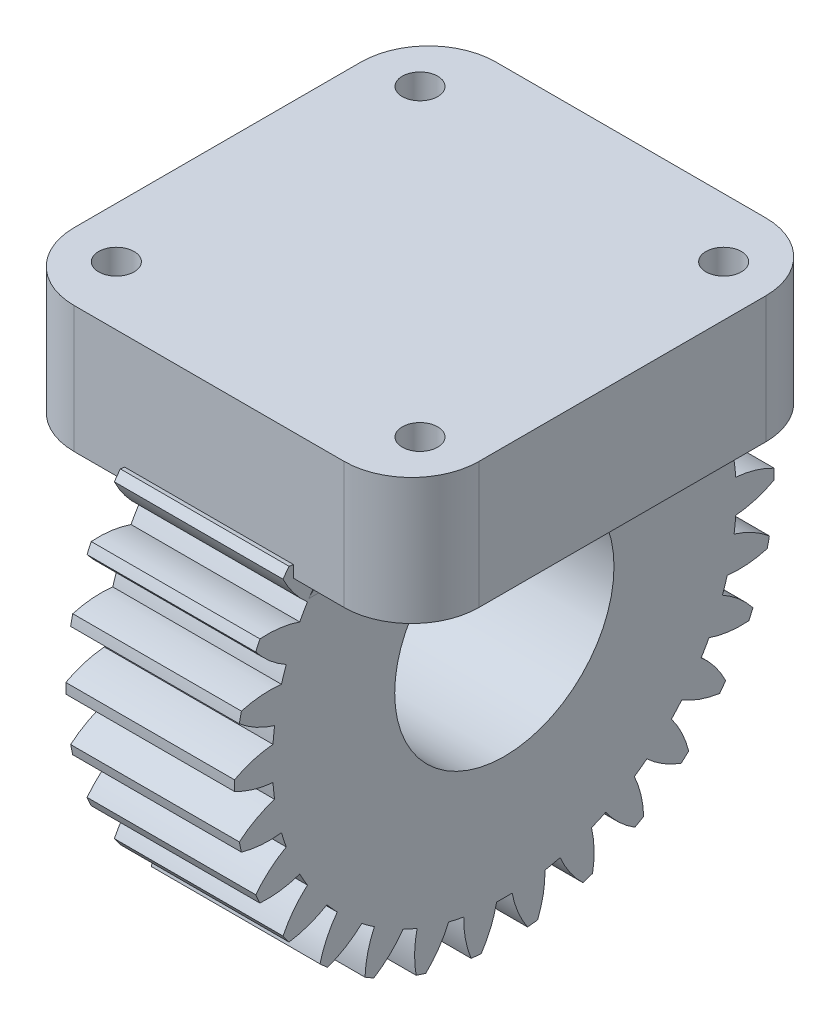
SolidWorks part; units mm, degrees
ref_plane "Front Plane" through (0, 0, 0) normal (0, 0, 1) x (1, 0, 0)
ref_plane "Top Plane" through (0, 0, 0) normal (0, 1, 0) x (1, 0, 0)
ref_plane "Right Plane" through (0, 0, 0) normal (1, 0, 0) x (0, 0, -1)
ref_plane "Plane1" through (30.4852, 0, 0) normal (1, 0, 0) x (0, 0, -1)
sketch "Sketch1" plane through (30.4852, 0, 0) normal (1, 0, 0) x (0, 0, -1)
  circle A0 centre (-23.9245, -5.8647) radius 13
  arc A1 (-55.9188, -6.4669) -> (-51.3536, -7.824) centre (-50.2847, 4.1283) ccw
  arc A2 (-51.3536, -7.824) -> (-51.1616, -9.6511) centre (-23.9245, -5.8647) ccw
  arc A3 (-51.1616, -9.6511) -> (-55.3448, -11.9278) centre (-47.631, -21.1199) ccw
  arc A4 (-55.3448, -11.9278) -> (-55.0945, -13.1057) centre (-23.9245, -5.8647) ccw
  arc A5 (-55.0945, -13.1057) -> (-50.3468, -13.4841) centre (-51.7863, -1.5707) ccw
  arc A6 (-50.3468, -13.4841) -> (-49.7791, -15.2312) centre (-23.9245, -5.8647) ccw
  arc A7 (-49.7791, -15.2312) -> (-53.3977, -18.3279) centre (-43.9412, -25.7154) ccw
  arc A8 (-53.3977, -18.3279) -> (-52.9079, -19.4281) centre (-23.9245, -5.8647) ccw
  arc A9 (-52.9079, -19.4281) -> (-48.1853, -18.8111) centre (-52.0702, -7.4573) ccw
  arc A10 (-48.1853, -18.8111) -> (-47.2667, -20.402) centre (-23.9245, -5.8647) ccw
  arc A11 (-47.2667, -20.402) -> (-50.1624, -24.1834) centre (-39.3766, -29.4434) ccw
  arc A12 (-50.1624, -24.1834) -> (-49.4545, -25.1577) centre (-23.9245, -5.8647) ccw
  arc A13 (-49.4545, -25.1577) -> (-44.9634, -23.5723) centre (-51.1241, -13.2744) ccw
  arc A14 (-44.9634, -23.5723) -> (-43.7342, -24.9375) centre (-23.9245, -5.8647) ccw
  arc A15 (-43.7342, -24.9375) -> (-45.7803, -29.2383) centre (-34.1367, -32.1408) ccw
  arc A16 (-45.7803, -29.2383) -> (-44.8854, -30.0441) centre (-23.9245, -5.8647) ccw
  arc A17 (-44.8854, -30.0441) -> (-40.8221, -27.5596) centre (-48.9891, -18.7676) ccw
  arc A18 (-40.8221, -27.5596) -> (-39.3358, -28.6394) centre (-23.9245, -5.8647) ccw
  arc A19 (-39.3358, -28.6394) -> (-40.4431, -33.2716) centre (-28.4504, -33.6898) ccw
  arc A20 (-40.4431, -33.2716) -> (-39.4002, -33.8737) centre (-23.9245, -5.8647) ccw
  arc A21 (-39.4002, -33.8737) -> (-35.9422, -30.5987) centre (-45.7588, -23.6968) ccw
  arc A22 (-35.9422, -30.5987) -> (-34.264, -31.3459) centre (-23.9245, -5.8647) ccw
  arc A23 (-34.264, -31.3459) -> (-34.3839, -36.1071) centre (-22.5663, -34.0228) ccw
  arc A24 (-34.3839, -36.1071) -> (-33.2386, -36.4792) centre (-23.9245, -5.8647) ccw
  arc A25 (-33.2386, -36.4792) -> (-30.5371, -32.5568) centre (-41.5741, -27.8468) ccw
  arc A26 (-30.5371, -32.5568) -> (-28.7402, -32.9388) centre (-23.9245, -5.8647) ccw
  arc A27 (-28.7402, -32.9388) -> (-27.8676, -37.6209) centre (-16.7416, -33.1251) ccw
  arc A28 (-27.8676, -37.6209) -> (-26.67, -37.7467) centre (-23.9245, -5.8647) ccw
  arc A29 (-26.67, -37.7467) -> (-24.843, -33.3484) centre (-36.6181, -31.036) ccw
  arc A30 (-24.843, -33.3484) -> (-23.0059, -33.3484) centre (-23.9245, -5.8647) ccw
  arc A31 (-23.0059, -33.3484) -> (-21.179, -37.7467) centre (-11.2308, -31.036) ccw
  arc A32 (-21.179, -37.7467) -> (-19.9813, -37.6209) centre (-23.9245, -5.8647) ccw
  arc A33 (-19.9813, -37.6209) -> (-19.1088, -32.9388) centre (-31.1073, -33.1251) ccw
  arc A34 (-19.1088, -32.9388) -> (-17.3118, -32.5568) centre (-23.9245, -5.8647) ccw
  arc A35 (-17.3118, -32.5568) -> (-14.6103, -36.4792) centre (-6.2748, -27.8468) ccw
  arc A36 (-14.6103, -36.4792) -> (-13.465, -36.1071) centre (-23.9245, -5.8647) ccw
  arc A37 (-13.465, -36.1071) -> (-13.585, -31.3459) centre (-25.2826, -34.0228) ccw
  arc A38 (-13.585, -31.3459) -> (-11.9067, -30.5987) centre (-23.9245, -5.8647) ccw
  arc A39 (-11.9067, -30.5987) -> (-8.4488, -33.8737) centre (-2.0902, -23.6968) ccw
  arc A40 (-8.4488, -33.8737) -> (-7.4059, -33.2716) centre (-23.9245, -5.8647) ccw
  arc A41 (-7.4059, -33.2716) -> (-8.5131, -28.6394) centre (-19.3986, -33.6898) ccw
  arc A42 (-8.5131, -28.6394) -> (-7.0269, -27.5596) centre (-23.9245, -5.8647) ccw
  arc A43 (-7.0269, -27.5596) -> (-2.9636, -30.0441) centre (1.1402, -18.7676) ccw
  arc A44 (-2.9636, -30.0441) -> (-2.0686, -29.2383) centre (-23.9245, -5.8647) ccw
  arc A45 (-2.0686, -29.2383) -> (-4.1148, -24.9375) centre (-13.7123, -32.1408) ccw
  arc A46 (-4.1148, -24.9375) -> (-2.8855, -23.5723) centre (-23.9245, -5.8647) ccw
  arc A47 (-2.8855, -23.5723) -> (1.6056, -25.1577) centre (3.2751, -13.2744) ccw
  arc A48 (1.6056, -25.1577) -> (2.3134, -24.1834) centre (-23.9245, -5.8647) ccw
  arc A49 (2.3134, -24.1834) -> (-0.5822, -20.402) centre (-8.4724, -29.4434) ccw
  arc A50 (-0.5822, -20.402) -> (0.3363, -18.8111) centre (-23.9245, -5.8647) ccw
  arc A51 (0.3363, -18.8111) -> (5.0589, -19.4281) centre (4.2213, -7.4573) ccw
  arc A52 (5.0589, -19.4281) -> (5.5487, -18.3279) centre (-23.9245, -5.8647) ccw
  arc A53 (5.5487, -18.3279) -> (1.9302, -15.2312) centre (-3.9078, -25.7154) ccw
  arc A54 (1.9302, -15.2312) -> (2.4979, -13.4841) centre (-23.9245, -5.8647) ccw
  arc A55 (2.4979, -13.4841) -> (7.2455, -13.1057) centre (3.9373, -1.5707) ccw
  arc A56 (7.2455, -13.1057) -> (7.4959, -11.9278) centre (-23.9245, -5.8647) ccw
  arc A57 (7.4959, -11.9278) -> (3.3126, -9.6511) centre (-0.218, -21.1199) ccw
  arc A58 (3.3126, -9.6511) -> (3.5046, -7.824) centre (-23.9245, -5.8647) ccw
  arc A59 (3.5046, -7.824) -> (8.0699, -6.4669) centre (2.4357, 4.1283) ccw
  arc A60 (8.0699, -6.4669) -> (8.0699, -5.2626) centre (-23.9245, -5.8647) ccw
  arc A61 (8.0699, -5.2626) -> (3.5046, -3.9054) centre (2.4357, -15.8577) ccw
  arc A62 (3.5046, -3.9054) -> (3.3126, -2.0784) centre (-23.9245, -5.8647) ccw
  arc A63 (3.3126, -2.0784) -> (7.4959, 0.1983) centre (-0.218, 9.3905) ccw
  arc A64 (7.4959, 0.1983) -> (7.2455, 1.3762) centre (-23.9245, -5.8647) ccw
  arc A65 (7.2455, 1.3762) -> (2.4979, 1.7546) centre (3.9373, -10.1588) ccw
  arc A66 (2.4979, 1.7546) -> (1.9302, 3.5018) centre (-23.9245, -5.8647) ccw
  arc A67 (1.9302, 3.5018) -> (5.5487, 6.5985) centre (-3.9078, 13.986) ccw
  arc A68 (5.5487, 6.5985) -> (5.0589, 7.6986) centre (-23.9245, -5.8647) ccw
  arc A69 (5.0589, 7.6986) -> (0.3363, 7.0816) centre (4.2213, -4.2721) ccw
  arc A70 (0.3363, 7.0816) -> (-0.5822, 8.6726) centre (-23.9245, -5.8647) ccw
  arc A71 (-0.5822, 8.6726) -> (2.3134, 12.4539) centre (-8.4724, 17.7139) ccw
  arc A72 (2.3134, 12.4539) -> (1.6056, 13.4282) centre (-23.9245, -5.8647) ccw
  arc A73 (1.6056, 13.4282) -> (-2.8855, 11.8428) centre (3.2751, 1.5449) ccw
  arc A74 (-2.8855, 11.8428) -> (-4.1148, 13.208) centre (-23.9245, -5.8647) ccw
  arc A75 (-4.1148, 13.208) -> (-2.0686, 17.5088) centre (-13.7123, 20.4113) ccw
  arc A76 (-2.0686, 17.5088) -> (-2.9636, 18.3146) centre (-23.9245, -5.8647) ccw
  arc A77 (-2.9636, 18.3146) -> (-7.0269, 15.8301) centre (1.1402, 7.0381) ccw
  arc A78 (-7.0269, 15.8301) -> (-8.5131, 16.9099) centre (-23.9245, -5.8647) ccw
  arc A79 (-8.5131, 16.9099) -> (-7.4059, 21.5421) centre (-19.3986, 21.9604) ccw
  arc A80 (-7.4059, 21.5421) -> (-8.4488, 22.1442) centre (-23.9245, -5.8647) ccw
  arc A81 (-8.4488, 22.1442) -> (-11.9067, 18.8692) centre (-2.0902, 11.9674) ccw
  arc A82 (-11.9067, 18.8692) -> (-13.585, 19.6164) centre (-23.9245, -5.8647) ccw
  arc A83 (-13.585, 19.6164) -> (-13.465, 24.3776) centre (-25.2826, 22.2933) ccw
  arc A84 (-13.465, 24.3776) -> (-14.6103, 24.7498) centre (-23.9245, -5.8647) ccw
  arc A85 (-14.6103, 24.7498) -> (-17.3118, 20.8274) centre (-6.2748, 16.1173) ccw
  arc A86 (-17.3118, 20.8274) -> (-19.1088, 21.2093) centre (-23.9245, -5.8647) ccw
  arc A87 (-19.1088, 21.2093) -> (-19.9813, 25.8914) centre (-31.1073, 21.3956) ccw
  arc A88 (-19.9813, 25.8914) -> (-21.179, 26.0173) centre (-23.9245, -5.8647) ccw
  arc A89 (-21.179, 26.0173) -> (-23.0059, 21.6189) centre (-11.2308, 19.3065) ccw
  arc A90 (-23.0059, 21.6189) -> (-24.843, 21.6189) centre (-23.9245, -5.8647) ccw
  arc A91 (-24.843, 21.6189) -> (-26.67, 26.0173) centre (-36.6181, 19.3065) ccw
  arc A92 (-26.67, 26.0173) -> (-27.8676, 25.8914) centre (-23.9245, -5.8647) ccw
  arc A93 (-27.8676, 25.8914) -> (-28.7402, 21.2093) centre (-16.7416, 21.3956) ccw
  arc A94 (-28.7402, 21.2093) -> (-30.5371, 20.8274) centre (-23.9245, -5.8647) ccw
  arc A95 (-30.5371, 20.8274) -> (-33.2386, 24.7498) centre (-41.5741, 16.1173) ccw
  arc A96 (-33.2386, 24.7498) -> (-34.3839, 24.3776) centre (-23.9245, -5.8647) ccw
  arc A97 (-34.3839, 24.3776) -> (-34.264, 19.6164) centre (-22.5663, 22.2933) ccw
  arc A98 (-34.264, 19.6164) -> (-35.9422, 18.8692) centre (-23.9245, -5.8647) ccw
  arc A99 (-35.9422, 18.8692) -> (-39.4002, 22.1442) centre (-45.7588, 11.9674) ccw
  arc A100 (-39.4002, 22.1442) -> (-40.4431, 21.5421) centre (-23.9245, -5.8647) ccw
  arc A101 (-40.4431, 21.5421) -> (-39.3358, 16.9099) centre (-28.4504, 21.9604) ccw
  arc A102 (-39.3358, 16.9099) -> (-40.8221, 15.8301) centre (-23.9245, -5.8647) ccw
  arc A103 (-40.8221, 15.8301) -> (-44.8854, 18.3146) centre (-48.9891, 7.0381) ccw
  arc A104 (-44.8854, 18.3146) -> (-45.7803, 17.5088) centre (-23.9245, -5.8647) ccw
  arc A105 (-45.7803, 17.5088) -> (-43.7342, 13.208) centre (-34.1367, 20.4113) ccw
  arc A106 (-43.7342, 13.208) -> (-44.9634, 11.8428) centre (-23.9245, -5.8647) ccw
  arc A107 (-44.9634, 11.8428) -> (-49.4545, 13.4282) centre (-51.1241, 1.5449) ccw
  arc A108 (-49.4545, 13.4282) -> (-50.1624, 12.4539) centre (-23.9245, -5.8647) ccw
  arc A109 (-50.1624, 12.4539) -> (-47.2667, 8.6726) centre (-39.3766, 17.7139) ccw
  arc A110 (-47.2667, 8.6726) -> (-48.1853, 7.0816) centre (-23.9245, -5.8647) ccw
  arc A111 (-48.1853, 7.0816) -> (-52.9079, 7.6986) centre (-52.0702, -4.2721) ccw
  arc A112 (-52.9079, 7.6986) -> (-53.3977, 6.5985) centre (-23.9245, -5.8647) ccw
  arc A113 (-53.3977, 6.5985) -> (-49.7791, 3.5018) centre (-43.9412, 13.986) ccw
  arc A114 (-49.7791, 3.5018) -> (-50.3468, 1.7546) centre (-23.9245, -5.8647) ccw
  arc A115 (-50.3468, 1.7546) -> (-55.0945, 1.3762) centre (-51.7863, -10.1588) ccw
  arc A116 (-55.0945, 1.3762) -> (-55.3448, 0.1983) centre (-23.9245, -5.8647) ccw
  arc A117 (-55.3448, 0.1983) -> (-51.1616, -2.0784) centre (-47.631, 9.3905) ccw
  arc A118 (-51.1616, -2.0784) -> (-51.3536, -3.9054) centre (-23.9245, -5.8647) ccw
  arc A119 (-51.3536, -3.9054) -> (-55.9188, -5.2626) centre (-50.2847, -15.8577) ccw
  arc A120 (-55.9188, -5.2626) -> (-55.9188, -6.4669) centre (-23.9245, -5.8647) ccw
extrude "Boss-Extrude1" add sketch "Sketch1" against normal blind 20
sketch "Sketch3" plane through (30.4852, 0, 0) normal (1, 0, 0) x (0, 0, -1)
  line L1 (-48.9245, 11.9354) -> (1.0755, 11.9354)
  line L2 (-48.9245, 11.9354) -> (-48.9245, 26.9354)
  line L3 (-48.9245, 26.9354) -> (1.0755, 26.9354)
  line L4 (1.0755, 11.9354) -> (1.0755, 26.9354)
  point P7 (-23.9245, 26.9354)
  dimension "D1" = 50
  dimension "D2" = 15
extrude "Boss-Extrude2" add sketch "Sketch3" along normal blind 14 and the other way blind 34
fillet "Fillet1" radius 3 2 edges at (10.4852, 11.9354, 23.9245) (30.4852, 11.9354, 23.9245)
sketch "Sketch4" plane through (0, 26.9354, 0) normal (0, 1, 0) x (1, 0, 0)
  circle A0 centre (2.4852, -5.9245) radius 2.1
  circle A1 centre (38.4852, -5.9245) radius 2.1
  circle A2 centre (38.4852, -41.9245) radius 2.1
  circle A3 centre (2.4852, -41.9245) radius 2.1
  point P6 (20.4852, -23.9245)
  dimension "D3" = 4.2
  dimension "D4" = 4.2
  dimension "D5" = 4.2
  dimension "D6" = 4.2
  dimension "D1" = 36
  dimension "D2" = 36
extrude "Cut-Extrude3" cut sketch "Sketch4" against normal blind 84
fillet "Fillet2" radius 8 4 edges at (-3.5148, 19.4354, 48.9245) (44.4852, 19.4354, 48.9245) (44.4852, 19.4354, -1.0755) (-3.5148, 19.4354, -1.0755)
